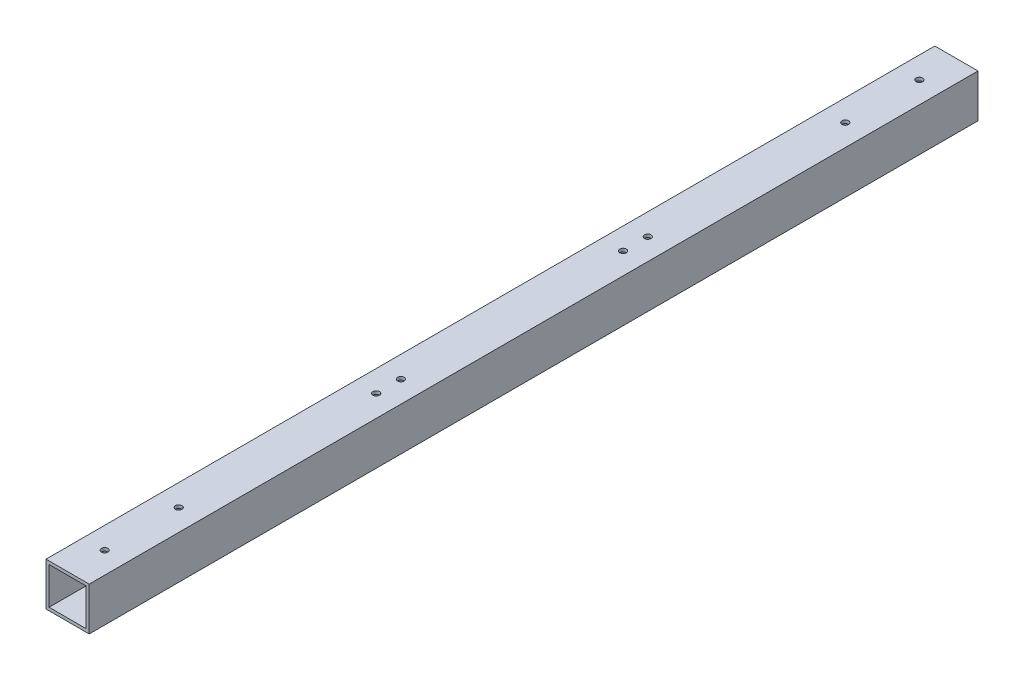
SolidWorks part; units mm, degrees
ref_plane "Front Plane" through (0, 0, 0) normal (0, 0, 1) x (1, 0, 0)
ref_plane "Top Plane" through (0, 0, 0) normal (0, 1, 0) x (1, 0, 0)
ref_plane "Right Plane" through (0, 0, 0) normal (1, 0, 0) x (0, 0, -1)
sketch "Sketch1" plane through (0, 0, 0) normal (0, 0, 1) x (1, 0, 0)
  line L1 (-22.225, -22.225) -> (22.225, -22.225)
  line L2 (-22.225, -22.225) -> (-22.225, 22.225)
  line L3 (-22.225, 22.225) -> (22.225, 22.225)
  line L4 (22.225, -22.225) -> (22.225, 22.225)
  line L5 (-22.225, -22.225) -> (22.225, 22.225) construction
  line L6 (-22.225, 22.225) -> (22.225, -22.225) construction
  line L7 (-19.05, -19.05) -> (19.05, -19.05)
  line L8 (-19.05, -19.05) -> (-19.05, 19.05)
  line L9 (-19.05, 19.05) -> (19.05, 19.05)
  line L10 (19.05, -19.05) -> (19.05, 19.05)
  line L11 (-19.05, -19.05) -> (19.05, 19.05) construction
  line L12 (-19.05, 19.05) -> (19.05, -19.05) construction
  point P0 (0, 0)
  point P6 (0, 0)
  dimension "D1" = 44.45
  dimension "D2" = 3.175
extrude "Boss-Extrude1" add sketch "Sketch1" along normal blind 914.4
sketch "Sketch2" plane through (0, 22.225, 0) normal (0, 1, 0) x (1, 0, 0)
  line L0 (0, 0) -> (0, -914.4) construction
  line L1 (22.225, -914.4) -> (-22.225, -914.4) construction
  line L2 (22.225, 0) -> (-22.225, 0) construction
  point P0 (0, -38.1)
  point P1 (0, -876.3)
  point P8 (0, -596.9)
  point P9 (0, -317.5)
  point P12 (22.225, -914.4)
  point P13 (0, -342.9)
  point P14 (22.225, 0)
  point P15 (0, -571.5)
  point P18 (0, -114.3)
  point P19 (0, -800.1)
  dimension "D1" = 279.4
  dimension "D2" = 838.2
  dimension "D3" = 38.1
  dimension "D4" = 279.4
  dimension "D5" = 914.4
  dimension "D6" = 685.8
  dimension "D7" = 228.6
  dimension "D8" = 228.6
  dimension "D9" = 114.3
hole_wizard "17/64 (0.26563) Diameter Hole1" positions "Sketch4" profile "Sketch5" hole size "17/64" standard "ANSI Inch" end condition through all
sketch "Sketch4" plane through (0, 22.225, 0) normal (0, 1, 0) x (1, 0, 0)
  point P0 (0, -38.1)
  point P6 (0, -876.3)
  point P10 (0, -317.5)
  point P13 (0, -596.9)
  point P16 (0, -114.3)
  point P19 (0, -342.9)
  point P22 (0, -571.5)
  point P25 (0, -800.1)
sketch "Sketch5" plane through (0, 22.225, 38.1) normal (1, 0, 0) x (0, 0, 1)
  line L0 (0, 0) -> (0, 44.45)
  line L1 (0, 44.45) -> (3.3735, 44.45)
  line L2 (3.3735, 44.45) -> (3.3735, 0)
  line L5 (3.3735, 0) -> (0, 0)
  line L11 (0, -6.35) -> (0, 107.95) construction
  dimension "Thru Hole Dia." = 6.747
  dimension "Thru Hole Depth" = 44.45
equation "\"D1@Sketch2\"=\"D2@Sketch2\"/3"
equation "\"D4@Sketch2\"=\"D2@Sketch2\"/3"
equation "\"D3@Sketch2\"=(\"D5@Sketch2\"-\"D2@Sketch2\")/2"
equation "\"D7@Sketch2\"=\"D6@Sketch2\"/3"
equation "\"D8@Sketch2\"=\"D6@Sketch2\"/3"
equation "\"D9@Sketch2\"=(\"D5@Sketch2\"-\"D6@Sketch2\")/2"
